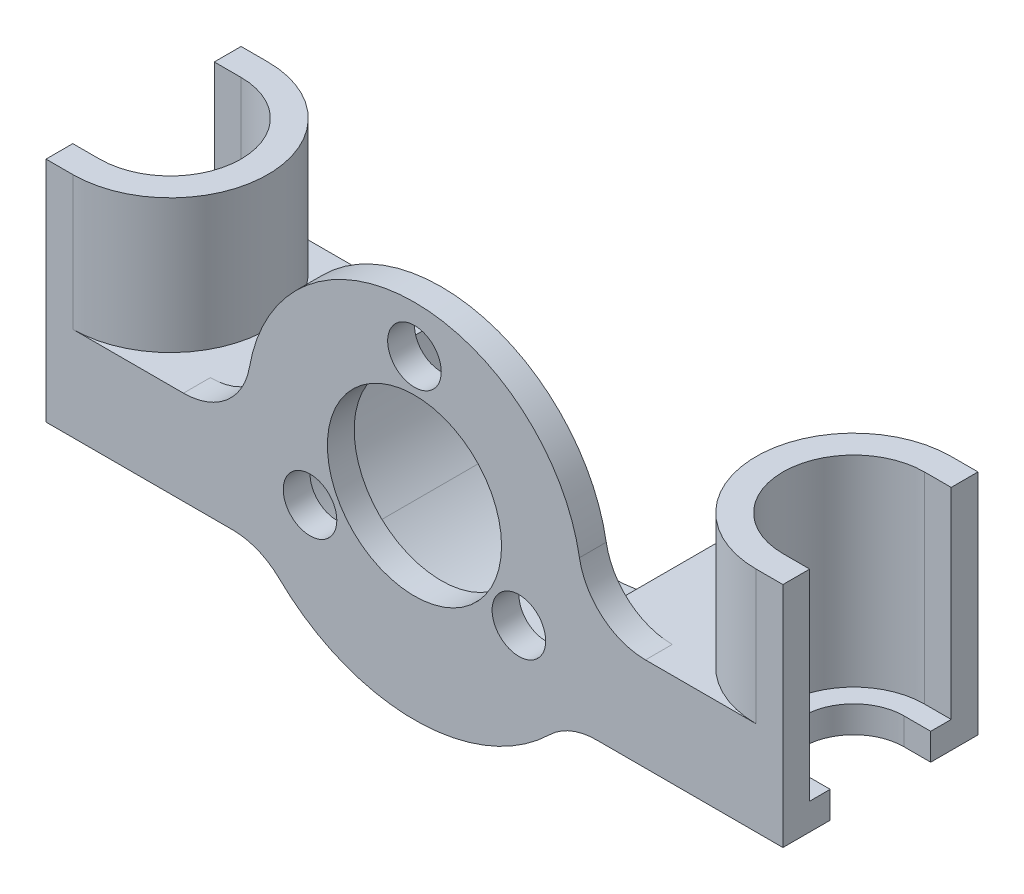
SolidWorks part; units mm, degrees
ref_plane "Plan de face" through (0, 0, 0) normal (0, 0, 1) x (1, 0, 0)
ref_plane "Plan de dessus" through (0, 0, 0) normal (0, 1, 0) x (1, 0, 0)
ref_plane "Plan de droite" through (0, 0, 0) normal (1, 0, 0) x (0, 0, -1)
sketch "Esquisse1" plane through (0, 0, 0) normal (0, 1, 0) x (1, 0, 0)
  line L0 (36.2599, -6.2545) -> (36.2599, -8.2545)
  line L1 (-18.7401, 6.3055) -> (-10.7401, 6.3055)
  line L2 (-18.7401, 6.3055) -> (-18.7401, 4.3055)
  line L3 (-18.7401, -8.2545) -> (-10.7401, -8.2545)
  line L4 (36.2599, 6.3055) -> (36.2599, 4.3055)
  line L5 (-18.7401, 4.3055) -> (-16.7401, 4.3055)
  line L6 (-21.3564, -0.9745) -> (63.6514, -0.9745) construction
  line L7 (-18.7401, -6.2545) -> (-16.7401, -6.2545)
  line L8 (-18.7401, -6.2545) -> (-18.7401, -8.2545)
  line L9 (36.2599, 4.3055) -> (34.2599, 4.3055)
  line L10 (28.2599, 6.3055) -> (36.2599, 6.3055)
  line L11 (36.2599, -6.2545) -> (34.2599, -6.2545)
  line L12 (-10.7401, 6.3055) -> (-8.7401, 6.3055)
  line L13 (28.2599, -8.2545) -> (36.2599, -8.2545)
  line L14 (-10.7401, -8.2545) -> (-8.7401, -8.2545)
  line L15 (26.2599, 6.3055) -> (28.2599, 6.3055)
  line L16 (28.2599, -8.2545) -> (26.2599, -8.2545)
  line L22 (-8.7401, 6.3055) -> (26.2599, 6.3055)
  line L26 (-8.7401, -8.2545) -> (26.2599, -8.2545)
  arc A0 (-16.7401, -6.2545) -> (-11.5556, -1.9745) centre (-16.7401, -0.9745) ccw
  arc A1 (34.2599, 4.3055) -> (29.0755, 0.0255) centre (34.2599, -0.9745) ccw
  arc A2 (-11.5556, 0.0255) -> (-16.7401, 4.3055) centre (-16.7401, -0.9745) ccw
  arc A3 (29.0755, -1.9745) -> (34.2599, -6.2545) centre (34.2599, -0.9745) ccw
  arc A4 (-11.5556, -1.9745) -> (-11.5556, 0.0255) centre (-16.7401, -0.9745) ccw
  arc A5 (29.0755, -1.9745) -> (29.0755, 0.0255) centre (34.2599, -0.9745) cw
  dimension "D1" = 10.56
  dimension "D7" = 2
  dimension "D26" = 5.28
  dimension "D2" = 10.56
  dimension "D3" = 2
  dimension "D4" = 2
  dimension "D5" = 2
  dimension "D6" = 51
  dimension "D8" = 2
extrude "Boss.-Extru.1" add sketch "Esquisse1" along normal blind 7
sketch "Esquisse4" plane through (0, 0, 0) normal (0, -1, 0) x (1, 0, 0)
  line L0 (8.7599, 8.2545) -> (8.7599, -6.3055) construction
  line L1 (34.2599, 4.7245) -> (36.2599, 4.7245)
  line L2 (-18.7401, 8.2545) -> (36.2599, 8.2545) construction
  line L3 (34.2599, 6.2545) -> (36.2599, 6.2545)
  line L4 (36.2599, 4.7245) -> (36.2599, 6.2545)
  line L5 (34.2599, -2.7755) -> (36.2599, -2.7755)
  line L6 (36.2599, -6.3055) -> (-18.7401, -6.3055) construction
  line L7 (34.2599, -4.3055) -> (36.2599, -4.3055)
  line L8 (36.2599, -2.7755) -> (36.2599, -4.3055)
  line L9 (-18.7401, -2.7755) -> (-18.7401, -4.3055)
  line L10 (-16.7401, -4.3055) -> (-18.7401, -4.3055)
  line L11 (-16.7401, -2.7755) -> (-18.7401, -2.7755)
  line L12 (-18.7401, 4.7245) -> (-18.7401, 6.2545)
  line L13 (-16.7401, 6.2545) -> (-18.7401, 6.2545)
  line L14 (-16.7401, 4.7245) -> (-18.7401, 4.7245)
  arc A0 (34.2599, 6.2545) -> (34.2599, -4.3055) centre (34.2599, 0.9745) ccw
  arc A1 (34.2599, 4.7245) -> (34.2599, -2.7755) centre (34.2599, 0.9745) ccw
  arc A2 (-16.7401, 4.7245) -> (-16.7401, -2.7755) centre (-16.7401, 0.9745) cw
  arc A3 (-16.7401, 6.2545) -> (-16.7401, -4.3055) centre (-16.7401, 0.9745) cw
  dimension "D1" = 7.5
extrude "Boss.-Extru.3" add sketch "Esquisse4" against normal blind 2
sketch "Esquisse2" plane through (0, 0, 8.2545) normal (0, 0, 1) x (1, 0, 0)
  line L0 (-18.7401, 0) -> (36.2599, 0) construction
  line L1 (8.7599, 9) -> (8.7599, 32.5037) construction
  line L3 (36.2599, 3.5) -> (-18.7401, 3.5) construction
  line L4 (36.2599, 7) -> (36.2599, 0) construction
  line L5 (-18.7401, 7) -> (-18.7401, 0) construction
  line L6 (-18.7401, 7) -> (36.2599, 7) construction
  ellipse E0 centre (8.7599, 9) end of major axis (-3.7401, 9) minor radius 12.5
  point P5 (8.7599, 7)
  dimension "D1" = 25
  dimension "D2" = 25
  dimension "D3" = 3.5
extrude "Enlèv. mat.-Extru.1" cut sketch "Esquisse2" against normal through all
sketch "Esquisse3" plane through (0, 0, 8.2545) normal (0, 0, 1) x (1, 0, 0)
  line L5 (-18.7401, 3.5) -> (36.2599, 3.5) construction
  line L6 (8.7599, 47.4932) -> (8.7599, -17.2302) construction
  line L7 (-18.7401, 7) -> (-18.7401, 0) construction
  line L8 (36.2599, 7) -> (36.2599, 0) construction
  circle A0 centre (8.7599, 9) radius 6.5
  circle A1 centre (8.7599, 18) radius 2
  circle A2 centre (16.5542, 4.5) radius 2
  circle A3 centre (0.9657, 4.5) radius 2
  circle A4 centre (8.7599, 9) radius 12.5
  arc A6 (-3.579, 7) -> (0.0853, 0) centre (8.7599, 9) ccw construction
  point P14 (8.7599, 3.5)
  point P25 (8.7599, 9)
  dimension "D3" = 13
  dimension "D4" = 4
  dimension "D1" = 25
  dimension "D5" = 9
  dimension "D6" = 3
extrude "Boss.-Extru.2" add sketch "Esquisse3" against normal blind 2
sketch "Esquisse6" plane through (0, 0, 8.2545) normal (0, 0, 1) x (1, 0, 0)
  line L0 (0.0853, 0) -> (-2.6089, 0)
  line L1 (-18.7401, 0) -> (0.0853, 0) construction
  line L2 (17.4346, 0) -> (20.1287, 0)
  line L3 (17.4346, 0) -> (36.2599, 0) construction
  arc A0 (-2.6089, 0) -> (20.1287, 0) centre (8.7599, 9) ccw
  arc A1 (0.0853, 0) -> (17.4346, 0) centre (8.7599, 9) ccw
  dimension "D1" = 2
extrude "Boss.-Extru.4" add sketch "Esquisse6" against normal up to surface (14.56 mm away) up to face at (-10.3854, 3.4257, -6.3055)
fillet "Congé2" radius 5 4 edges at (20.1287, 0, 0.9745) (-2.6089, 0, 0.9745) (-3.579, 7, 7.2545)
sketch "Esquisse7" plane through (0, 7, 0) normal (0, 1, 0) x (1, 0, 0)
  line L0 (36.2599, -8.2545) -> (36.2599, -6.2545)
  line L1 (36.2599, -6.2545) -> (34.2599, -6.2545)
  line L2 (36.2599, -8.2545) -> (34.2599, -8.2545)
  line L3 (36.2599, 4.3055) -> (34.2599, 4.3055)
  line L4 (36.2599, 4.3055) -> (36.2599, 6.3055)
  line L5 (36.2599, 6.3055) -> (34.2599, 6.3055)
  line L6 (36.2599, 6.3055) -> (-18.7401, 6.3055) construction
  line L7 (8.7599, 6.3055) -> (8.7599, -9.2971) construction
  line L8 (-18.7401, 6.3055) -> (-16.7401, 6.3055)
  line L9 (-18.7401, 4.3055) -> (-18.7401, 6.3055)
  line L10 (-18.7401, 4.3055) -> (-16.7401, 4.3055)
  line L11 (-18.7401, -8.2545) -> (-16.7401, -8.2545)
  line L12 (-18.7401, -6.2545) -> (-16.7401, -6.2545)
  line L13 (-18.7401, -8.2545) -> (-18.7401, -6.2545)
  arc A0 (34.2599, 6.3055) -> (34.2599, -8.2545) centre (34.2599, -0.9745) ccw
  arc A1 (34.2599, 4.3055) -> (34.2599, -6.2545) centre (34.2599, -0.9745) ccw
  arc A2 (-16.7401, 4.3055) -> (-16.7401, -6.2545) centre (-16.7401, -0.9745) cw
  arc A3 (-16.7401, 6.3055) -> (-16.7401, -8.2545) centre (-16.7401, -0.9745) cw
extrude "Boss.-Extru.5" add sketch "Esquisse7" along normal blind 10
